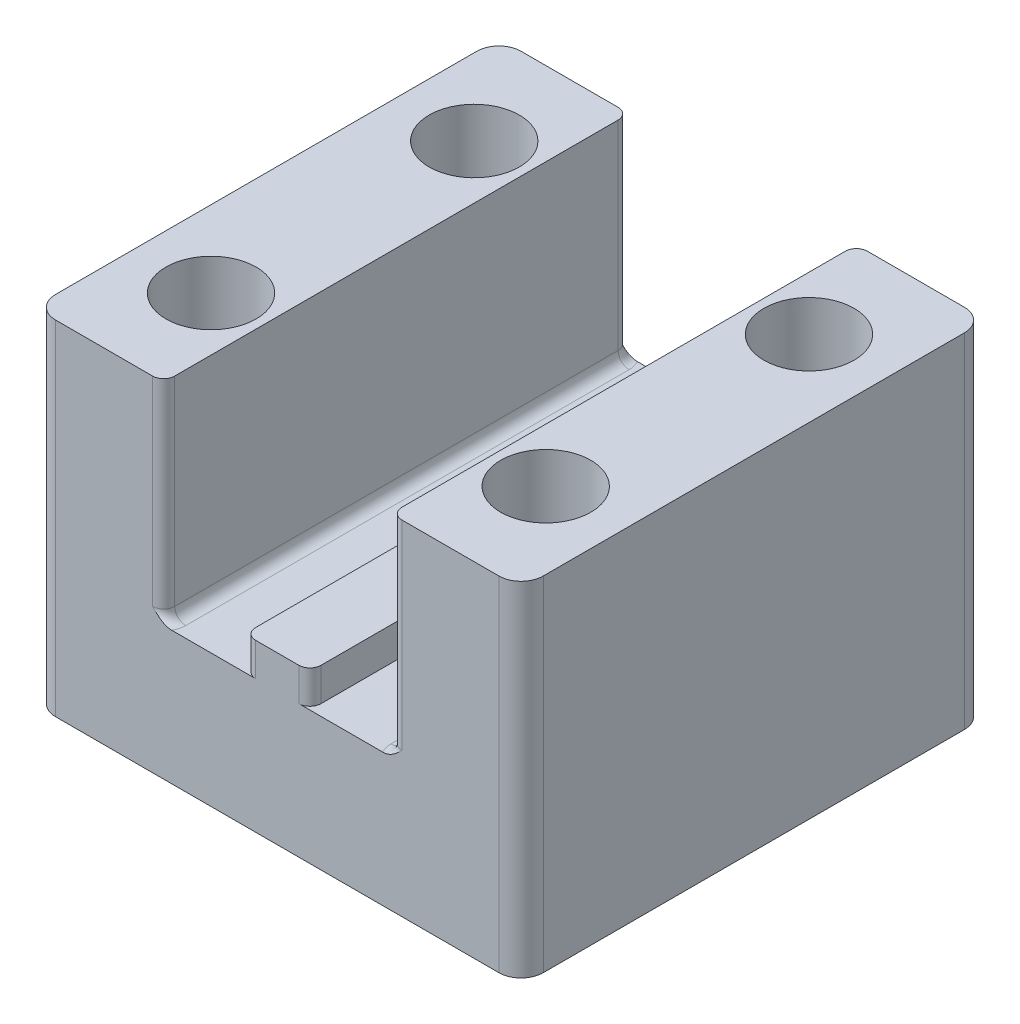
SolidWorks part; units mm, degrees
ref_plane "Plan de face" through (0, 0, 0) normal (0, 0, 1) x (1, 0, 0)
ref_plane "Plan de dessus" through (0, 0, 0) normal (0, 1, 0) x (1, 0, 0)
ref_plane "Plan de droite" through (0, 0, 0) normal (1, 0, 0) x (0, 0, -1)
sketch "Esquisse1" plane through (0, 0, 0) normal (0, 1, 0) x (1, 0, 0)
  line L0 (0, 14.8906) -> (0, 0) construction
  line L1 (0, 0) -> (19.0083, 0) construction
  line L3 (22, 21) -> (-22, 21)
  line L4 (22, 21) -> (22, -21)
  line L5 (22, -21) -> (-22, -21)
  line L6 (-22, 21) -> (-22, -21)
  line L7 (22, 21) -> (-22, -21) construction
  line L8 (22, -21) -> (-22, 21) construction
  circle A0 centre (-15.1, 11.875) radius 4.065
  circle A1 centre (15.1, 11.875) radius 4.065
  circle A2 centre (15.1, -11.875) radius 4.065
  circle A3 centre (-15.1, -11.875) radius 4.065
  dimension "D1" = 8.13
  dimension "D2" = 30.2
  dimension "D3" = 23.75
  dimension "D4" = 44
  dimension "D5" = 42
extrude "Boss.-Extru.1" add sketch "Esquisse1" along normal blind 12
sketch "Esquisse2" plane through (0, 12, 0) normal (0, 1, 0) x (1, 0, 0)
  line L0 (0, 21) -> (0, 0) construction
  line L1 (22, 21) -> (-22, 21) construction
  line L2 (-22, -21) -> (22, -21) construction
  line L3 (-2.95, -21) -> (2.95, -21)
  line L4 (-2.95, -21) -> (-2.95, 21)
  line L5 (-2.95, 21) -> (2.95, 21)
  line L6 (2.95, -21) -> (2.95, 21)
  line L7 (-2.95, -21) -> (2.95, 21) construction
  line L8 (-2.95, 21) -> (2.95, -21) construction
  line L9 (-22, 21) -> (-10.25, 21)
  line L10 (-22, 21) -> (-22, -21)
  line L11 (-22, -21) -> (-10.25, -21)
  line L12 (-10.25, 21) -> (-10.25, -21)
  line L13 (10.25, 21) -> (10.25, -21)
  line L14 (22, -21) -> (10.25, -21)
  line L15 (22, 21) -> (22, -21)
  line L16 (22, 21) -> (10.25, 21)
  circle A0 centre (15.1, 11.875) radius 4.065 construction
  circle A1 centre (15.1, -11.875) radius 4.065 construction
  circle A2 centre (-15.1, -11.875) radius 4.065 construction
  circle A3 centre (-15.1, 11.875) radius 4.065 construction
  circle A4 centre (15.1, 11.875) radius 4.065
  circle A5 centre (15.1, -11.875) radius 4.065
  circle A6 centre (-15.1, -11.875) radius 4.065
  circle A7 centre (-15.1, 11.875) radius 4.065
  dimension "D1" = 5.9
  dimension "D2" = 20.5
extrude "Boss.-Extru.2" add sketch "Esquisse2" along normal blind 19
sketch "Esquisse3" plane through (0, 31, 0) normal (0, 1, 0) x (1, 0, 0)
  line L4 (2.95, -21) -> (2.95, 21)
  line L5 (2.95, 21) -> (-2.95, 21)
  line L6 (-2.95, 21) -> (-2.95, -21)
  line L7 (-2.95, -21) -> (2.95, -21)
  line L8 (2.95, -21) -> (2.95, 21)
  line L9 (2.95, 21) -> (-2.95, 21)
  line L10 (-2.95, 21) -> (-2.95, -21)
  line L11 (-2.95, -21) -> (2.95, -21)
  dimension "D1" = 0
extrude "Enlèv. mat.-Extru.1" cut sketch "Esquisse3" against normal blind 16
sketch "Esquisse4" plane through (0, 0, 0) normal (0, -1, 0) x (1, 0, 0)
  line L0 (0, 21) -> (0, 0) construction
  line L1 (-22, 21) -> (22, 21) construction
  line L2 (0, 0) -> (22, 0) construction
  line L3 (22, 21) -> (22, -21) construction
  circle A0 centre (0, 12) radius 2.2
  circle A1 centre (0, -12) radius 2.2
  dimension "D1" = 4.4
  dimension "D2" = 24
extrude "Enlèv. mat.-Extru.2" [suppressed] cut sketch "Esquisse4" against normal through all
fillet "Congé1" radius 2 4 edges at (-22, 15.5, -21) (22, 15.5, -21) (22, 15.5, 21) (-22, 15.5, 21)
fillet "Congé2" radius 1 8 edges at (2.95, 13.5, 21) (-2.95, 13.5, 21) (2.95, 13.5, -21) (-2.95, 13.5, -21) (10.25, 21.5, -21) (10.25, 21.5, 21) (-10.25, 21.5, -21) (-10.25, 21.5, 21)
fillet "Congé3" radius 1 6 edges at (10.5429, 12, -20.7071) (10.5429, 12, 20.7071) (-10.5429, 12, 20.7071) (-10.5429, 12, -20.7071) (10.25, 12, 0) (-10.25, 12, 0)
sketch "Esquisse5" [suppressed] plane through (0, 0, 0) normal (0, -1, 0) x (1, 0, 0)
  circle A0 centre (0, -12) radius 3.65
  circle A1 centre (0, 12) radius 3.65
  dimension "D1" = 7.3
extrude "Enlèv. mat.-Extru.3" [suppressed] cut sketch "Esquisse5" against normal blind 8
